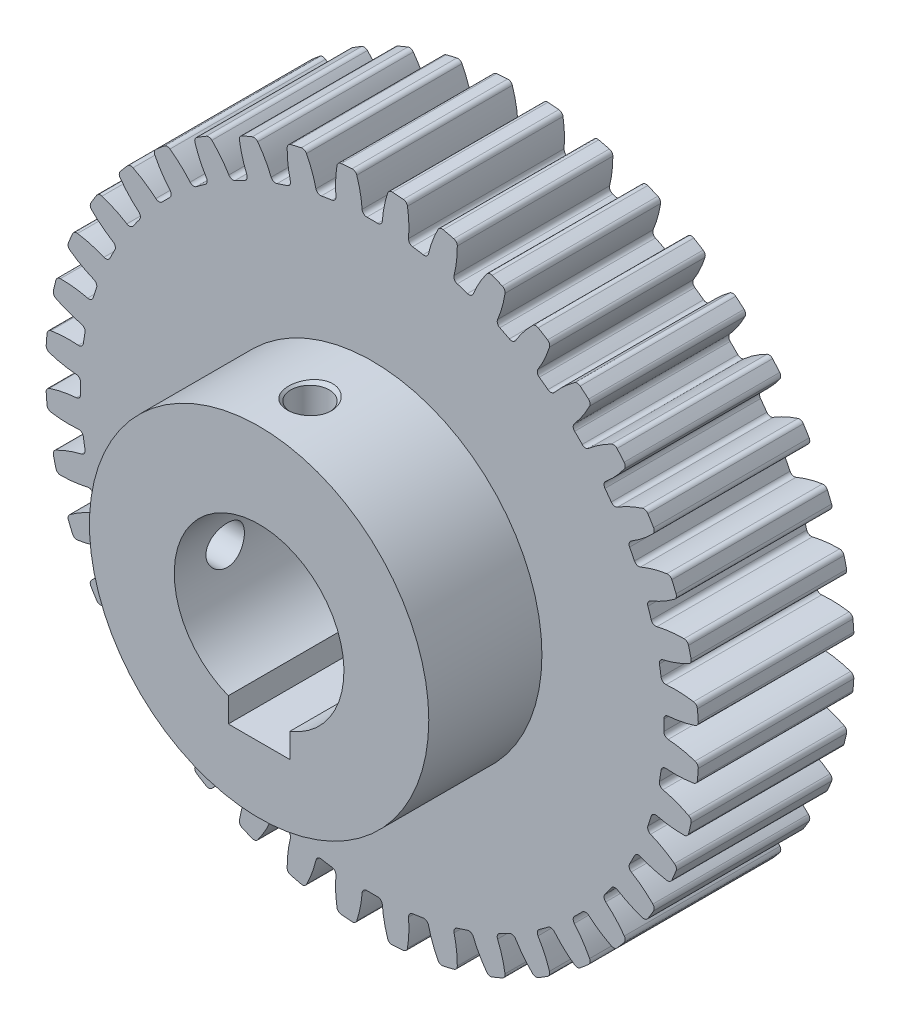
SolidWorks part; units mm, degrees
ref_plane "Ön Düzlem" through (0, 0, 0) normal (0, 0, 1) x (1, 0, 0)
ref_plane "Üst Düzlem" through (0, 0, 0) normal (0, 1, 0) x (1, 0, 0)
ref_plane "Sağ Düzlem" through (0, 0, 0) normal (1, 0, 0) x (0, 0, -1)
sketch "Çizim1" plane through (0, 0, 0) normal (0, 0, 1) x (1, 0, 0)
  circle A0 centre (0, 0) radius 57.75
  dimension "D1" = 115.5
extrude "Yükseklik-Ekstrüzyon1" add sketch "Çizim1" along normal mid plane 27.5
sketch "Çizim2" plane through (0, 0, 13.75) normal (0, 0, 1) x (1, 0, 0)
  line L0 (0, 0) -> (0, 57.75) construction
  line L1 (0, 0) -> (-2.2673, 57.7055) construction
  line L2 (0, 0) -> (-1.7426, 51.533) construction
  line L3 (-3.1643, 58.2578) -> (6.2691, 34.8349) construction
  line L4 (1.7426, 51.533) -> (1.7426, 51.5287)
  circle A0 centre (0, 0) radius 57.75 construction
  circle A1 centre (0, 0) radius 55 construction
  arc A2 (1.7426, 51.533) -> (-1.7426, 51.533) centre (0, 0) ccw
  arc A3 (-3.1643, 58.2578) -> (-1.7426, 51.533) centre (-21.5224, 50.8642) cw
  arc A4 (3.1643, 58.2578) -> (1.7426, 51.533) centre (21.5224, 50.8642) ccw
  arc A5 (-3.1643, 58.2578) -> (3.1643, 58.2578) centre (0, 0) cw
  point P12 (-2.1593, 54.9576)
  circle M9 centre (0, 0) radius 57.75
  dimension "D2" = 103.125
  dimension "D3" = 110
  dimension "D1" = 2.25
  dimension "D4" = 20
extrude "Kes-Ekstrüzyon2" cut sketch "Çizim2" against normal blind 27.5 contours A4 A3 A2 M9 region at (0, 54.9241, 13.75)
fillet "Radyus1" radius 0.825 4 edges at (2.9402, 57.6751, 0) (1.7426, 51.533, 0) (-2.9402, 57.6751, 0) (-1.7426, 51.533, 0)
pattern_circular "Dairesel Kaplama1" count 40 over 360 about axis through (0, 0, 13.75) along (0, 0, 1) of "Kes-Ekstrüzyon2", "Radyus1"
sketch "Çizim3" plane through (0, 0, 13.75) normal (0, 0, 1) x (1, 0, 0)
  circle A0 centre (0, 0) radius 30
  dimension "D1" = 60
extrude "Yükseklik-Ekstrüzyon2" add sketch "Çizim3" along normal blind 20
sketch "Çizim4" plane through (0, 0, 33.75) normal (0, 0, 1) x (1, 0, 0)
  circle A0 centre (0, 0) radius 15
  dimension "D1" = 30
extrude "Kes-Ekstrüzyon3" cut sketch "Çizim4" against normal through all
ref_plane "Düzlem1" through (0, 30, 0) normal (0, 1, 0) x (1, 0, 0)
hole_wizard "M8 Dişli Delik1" positions "Çizim7" profile "Çizim8" tap size "M8" standard "ISO"
sketch "Çizim7" plane through (0, 30, 0) normal (0, 1, 0) x (1, 0, 0)
  line L0 (-30, -33.75) -> (30, -33.75) construction
  point P0 (0, -24.75)
  dimension "D1" = 9
sketch "Çizim8" plane through (0, 30, 24.75) normal (1, 0, 0) x (0, 0, 1)
  line L0 (0, 0) -> (0, 24.2929)
  line L1 (0, 24.2929) -> (3.4, 22.25)
  line L2 (3.4, 22.25) -> (3.4, 0.625)
  line L3 (3.4, 0.625) -> (4.025, 0)
  line L5 (4.025, 0) -> (0, 0)
  line L6 (-3.4, 0.625) -> (-4.025, 0) construction
  line L10 (0, 24.2929) -> (-3.4, 22.25) construction
  line L11 (0, -6.35) -> (0, 107.95) construction
  dimension "Tap Drill Dia." = 6.8
  dimension "Tap Drill Depth" = 22.25
  dimension "Near C'Sink Dia." = 8.05
  dimension "Near C'Sink Angle" = 90
  dimension "Drill Angle" = 118
cosmetic thread "Delik Dişi1" parameters "D1"=15.3904, "D2"=8
pattern_circular "Dairesel Kaplama2" count 2 over 90 about axis through (0, 0, 33.75) along (0, 0, 1) of "M8 Dişli Delik1"
cosmetic thread "Delik Dişi2" parameters "D1"=15.3904, "D2"=8
sketch "Çizim9" plane through (0, 0, 0) normal (0, 1, 0) x (1, 0, 0)
  line L0 (-30, -33.75) -> (30, -33.75) construction
  line L1 (5.4436, -33.75) -> (-5.4436, -33.75)
  line L2 (5.4436, -33.75) -> (5.4436, 13.75)
  line L3 (5.4436, 13.75) -> (-5.4436, 13.75)
  line L4 (-5.4436, -33.75) -> (-5.4436, 13.75)
  line L6 (0, -33.75) -> (0, -43.2311) construction
  point P6 (0, -33.75)
extrude "Kes-Ekstrüzyon4" cut sketch "Çizim9" against normal blind 18.3
equation "\"m\"= 2.75'modül"
equation "\"z\"= 40'diş sayısı"
equation "\"Pa\"= 20derece'profil açısı "
equation "\"Do\"= \"m\" * \"z\"'bölüm dairesi çapı"
equation "\"Da\"= \"Do\" + ( \"m\" * 2 )'diş üstü çapı"
equation "\"Df\"= \"Do\" - ( \"m\" * 2.5 )'diş dibi çapı"
equation "\"a\"= 360 / ( \"z\" * 4 )'tasarım açısı"
equation "\"r\"= \"m\" * 0.3'diş dibi radyusu"
equation "\"b\"= \"m\" * 10'diş genişliği"
equation "\"D1@Çizim1\"=\"Da\""
equation "\"D1@Yükseklik-Ekstrüzyon1\"=\"b\""
equation "\"D1@Çizim2\"=\"a\""
equation "\"D2@Çizim2\"=\"Df\""
equation "\"D3@Çizim2\"=\"Do\""
equation "\"D4@Çizim2\"=\"Pa\""
equation "\"D1@Radyus1\"=\"r\""
equation "\"D1@Dairesel Kaplama1\"=\"z\""
